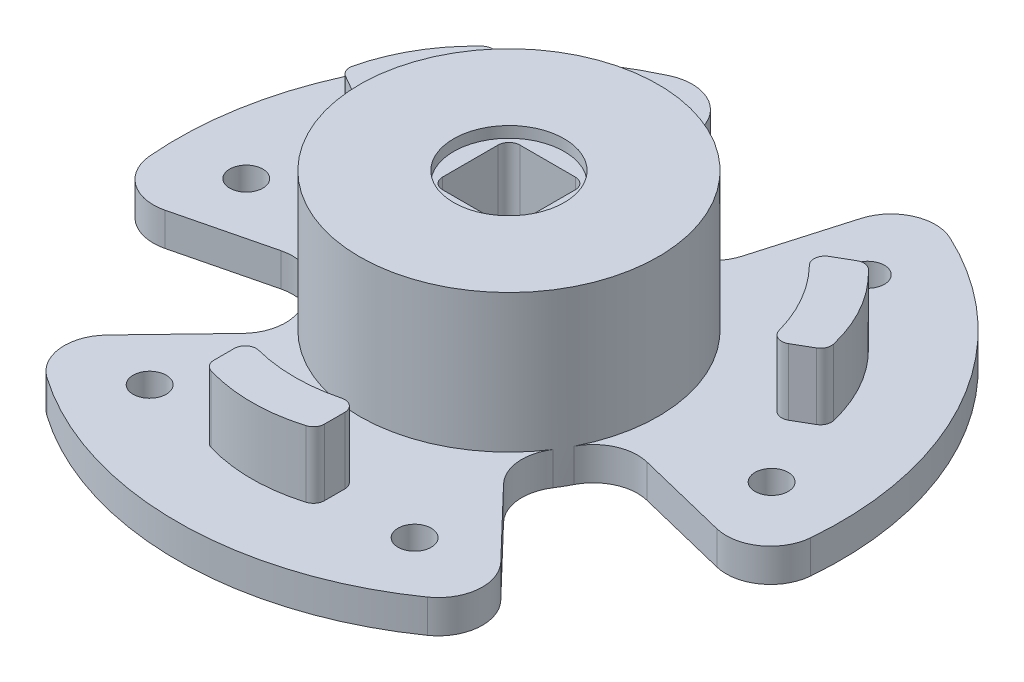
SolidWorks part; units mm, degrees
ref_plane "Front Plane" through (0, 0, 0) normal (0, 0, 1) x (1, 0, 0)
ref_plane "Top Plane" through (0, 0, 0) normal (0, 1, 0) x (1, 0, 0)
ref_plane "Right Plane" through (0, 0, 0) normal (1, 0, 0) x (0, 0, -1)
sketch "Sketch1" plane through (0, 0, 0) normal (0, 1, 0) x (1, 0, 0)
  circle A0 centre (0, 0) radius 30
extrude "Boss-Extrude1" add sketch "Sketch1" along normal blind 2.5 and the other way blind 0.5 contours A0
sketch "Sketch2" plane through (0, 2.5, 0) normal (0, 1, 0) x (1, 0, 0)
  circle A0 centre (0, 0) radius 13.5
extrude "Boss-Extrude2" add sketch "Sketch2" along normal blind 12.5
sketch "Sketch3" plane through (0, 15, 0) normal (0, 1, 0) x (1, 0, 0)
  line L6 (0, 30) -> (0, -30) construction
  line L7 (-30, 0) -> (30, 0) construction
  circle A1 centre (0, 0) radius 30 construction
  circle A2 centre (0, 0) radius 5
sketch "Sketch4" plane through (0, 15, 0) normal (0, 1, 0) x (1, 0, 0)
  line L2 (-3.5, 3.5) -> (3.5, 3.5)
  line L3 (-3.5, 3.5) -> (-3.5, -3.5)
  line L4 (-3.5, -3.5) -> (3.5, -3.5)
  line L5 (3.5, 3.5) -> (3.5, -3.5)
  dimension "D1" = 7
  dimension "D2" = 7
  dimension "D3" = 3.5
  dimension "D4" = 3.5
extrude "Cut-Extrude2" cut sketch "Sketch4" against normal blind 17.5 contours L2 L5 L4 L3
fillet "Fillet1" radius 1 4 edges at (3.5, 7.25, 3.5) (3.5, 7.25, -3.5) (-3.5, 7.25, -3.5) (-3.5, 7.25, 3.5)
extrude "Cut-Extrude3" cut sketch "Sketch3" against normal blind 1 contours A2
sketch "Sketch5" plane through (0, 2.5, 0) normal (0, 1, 0) x (1, 0, 0)
  line L1 (-30, 0) -> (30, 0) construction
  line L2 (0, 0) -> (-15, 25.9808) construction
  line L3 (0, 0) -> (15, 25.9808) construction
  line L4 (0, 0) -> (30, 0) construction
  line L5 (0, 0) -> (-15, -25.9808) construction
  line L6 (0, 0) -> (15, -25.9808) construction
  circle A0 centre (0, 0) radius 30 construction
  dimension "D1" = 60
  dimension "D2" = 60
  dimension "D3" = 60
  dimension "D4" = 60
  dimension "D5" = 60
sketch "Sketch6" plane through (0, 2.5, 0) normal (0, 1, 0) x (1, 0, 0)
  line L0 (0, 0) -> (-15, 25.9808) construction
  line L1 (0, 0) -> (15, 25.9808) construction
  line L2 (-30, 0) -> (30, 0) construction
  circle A0 centre (-11.875, 20.5681) radius 1.5
  circle A1 centre (11.875, 20.5681) radius 1.5
  circle A2 centre (23.75, 0) radius 1.5
  circle A3 centre (-23.75, 0) radius 1.5
  circle A4 centre (-11.9788, -20.5078) radius 1.5
  circle A5 centre (11.9788, -20.5078) radius 1.5
  dimension "D1" = 23.75
  dimension "D2" = 23.75
  dimension "D4" = 23.75
  dimension "D5" = 23.75
  dimension "D3" = 23.75
  dimension "D6" = 23.75
extrude "Cut-Extrude4" cut sketch "Sketch6" against normal blind 6
sketch "Sketch7" plane through (0, 2.5, 0) normal (0, 1, 0) x (1, 0, 0)
  line L0 (-8.353, 28.8137) -> (-3.7589, 12.9661)
  line L1 (8.353, 28.8137) -> (3.7589, 12.9661)
  circle A0 centre (0, 0) radius 30 construction
  circle A1 centre (0, 0) radius 13.5 construction
  arc A2 (-8.353, 28.8137) -> (8.353, 28.8137) centre (0, 0) cw
  arc A3 (-3.7589, 12.9661) -> (3.7589, 12.9661) centre (0, 0) cw
extrude "Cut-Extrude5" cut sketch "Sketch7" against normal blind 6
fillet "Fillet2" radius 4 4 edges at (-8.353, 1, -28.8137) (8.353, 1, -28.8137) (3.7589, 1, -12.9661) (-3.7589, 1, -12.9661)
pattern_circular "CirPattern1" count 3 over 360 about axis through (0, 15, 0) along (0, 1, 0) of "Cut-Extrude5", "Fillet2"
sketch "Sketch9" plane through (0, 2.5, 0) normal (0, 1, 0) x (1, 0, 0)
  line L0 (0, -13.5) -> (7.7942, -13.5) construction
  line L1 (0, 0) -> (15, -25.9808) construction
  line L2 (7.7942, -13.5) -> (-7.7942, -13.5) construction
  line L3 (0, 0) -> (-15, -25.9808) construction
  line L4 (0, -13.5) -> (0, -18.5) construction
  line L5 (0, -18.5) -> (-4.9956, -18.5) construction
  line L6 (-4.9956, -18.5) -> (5.0044, -18.5) construction
  line L8 (5.0044, -18.5) -> (5.0044, -22.4106)
  line L10 (-4.9956, -22.4106) -> (-4.9956, -18.5)
  arc A0 (-11.328, -7.3435) -> (11.328, -7.3435) centre (0, 0) ccw construction
  arc A1 (-4.9956, -18.5) -> (5.0044, -18.5) centre (0.0044, -4.3579) ccw
  arc A2 (-4.9956, -22.4106) -> (5.0044, -22.4106) centre (0.0044, -8.2684) ccw
  dimension "D1" = 10
extrude "Boss-Extrude3" add sketch "Sketch9" along normal blind 6
fillet "Fillet3" radius 1 4 edges at (5.0044, 5.5, 18.5) (5.0044, 5.5, 22.4106) (-4.9956, 5.5, 22.4106) (-4.9956, 5.5, 18.5)
pattern_circular "CirPattern2" count 3 over 360 about axis through (0, 15, 0) along (0, 1, 0) of "Boss-Extrude3", "Fillet3"
